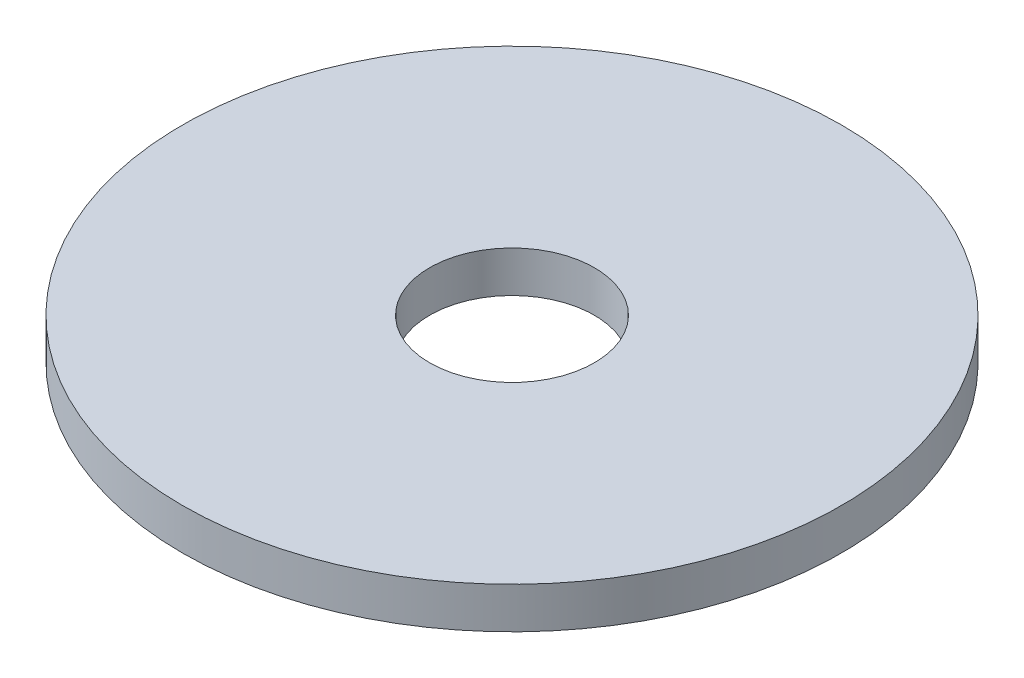
SolidWorks part; units mm, degrees
ref_plane "前视基准面" through (0, 0, 0) normal (0, 0, 1) x (1, 0, 0)
ref_plane "上视基准面" through (0, 0, 0) normal (0, 1, 0) x (1, 0, 0)
ref_plane "右视基准面" through (0, 0, 0) normal (1, 0, 0) x (0, 0, -1)
other "Configuration Table"
ref_plane "alpha0" through (0, 0, 0) normal (0, 1, 0) x (1, 0, 0)
ref_axis "axis" through (0, -0.25, 0) along (0, 1, 0)
sketch "草图1" plane through (0, 0, 0) normal (0, 1, 0) x (1, 0, 0)
  circle A0 centre (0, 0) radius 10
  circle A1 centre (0, 0) radius 40
extrude "顶盖" add sketch "草图1" along normal blind 5
